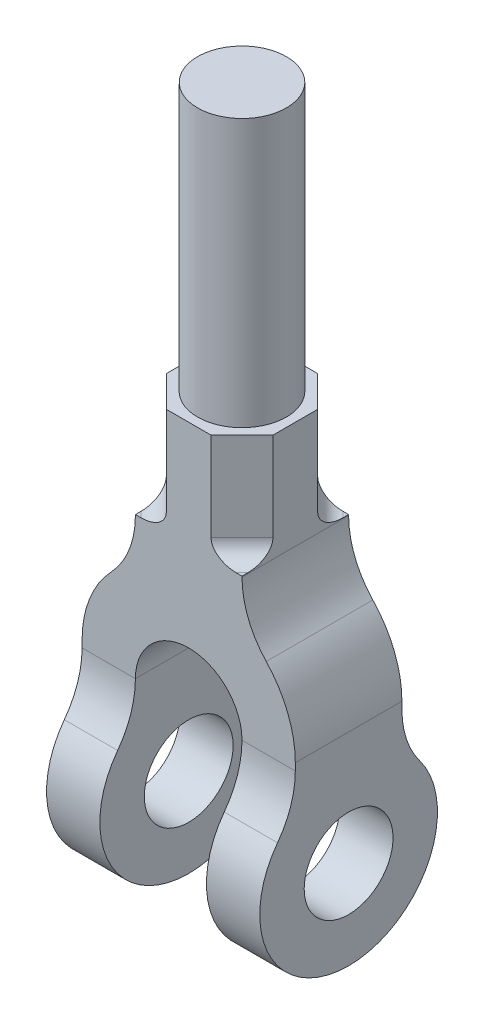
SolidWorks part; units mm, degrees
ref_plane "Front Plane" through (0, 0, 0) normal (0, 0, 1) x (1, 0, 0)
ref_plane "Top Plane" through (0, 0, 0) normal (0, 1, 0) x (1, 0, 0)
ref_plane "Right Plane" through (0, 0, 0) normal (1, 0, 0) x (0, 0, -1)
sketch "Sketch1" plane through (0, 0, 0) normal (0, 0, 1) x (1, 0, 0)
  line L1 (-60, -125) -> (60, -125)
  line L2 (-60, -125) -> (-60, 125)
  line L3 (-60, 125) -> (60, 125)
  line L4 (60, -125) -> (60, 125)
  line L5 (-60, -125) -> (60, 125) construction
  line L6 (-60, 125) -> (60, -125) construction
  point P0 (0, 0)
  dimension "D1" = 250
  dimension "D2" = 120
extrude "Boss-Extrude1" add sketch "Sketch1" along normal blind 100
sketch "Sketch2" plane through (0, 0, 100) normal (0, 0, 1) x (1, 0, 0)
  line L0 (0, 149.5031) -> (0, -100.4969) construction
  line L1 (60, 125) -> (-60, 125) construction
  line L2 (-30, 125) -> (-30, 64.4983)
  line L3 (30, 125) -> (30, 64.4983)
  line L4 (-30, -15) -> (-30, -125)
  line L7 (30, -15) -> (30, -125)
  arc A0 (-43.6364, 30.1809) -> (-30, -62.9615) centre (0, -11) ccw
  arc A1 (30, -15) -> (-30, -15) centre (0, -15) ccw
  arc A2 (-30, 64.4983) -> (-43.6364, 30.1809) centre (-80, 64.4983) cw
  arc A3 (30, 64.4983) -> (43.6364, 30.1809) centre (80, 64.4983) ccw
  arc A4 (30, -62.9615) -> (43.6364, 30.1809) centre (0, -11) ccw
  line M4 (60, -125) -> (60, 125)
  line M5 (60, 125) -> (-60, 125)
  line M6 (-60, 125) -> (-60, -125)
  line M7 (-60, -125) -> (60, -125)
  dimension "D1" = 120
  dimension "D2" = 60
  dimension "D7" = 50
  dimension "D3" = 4
  dimension "D4" = 140
  dimension "D5" = 30
  dimension "D6" = 0
  dimension "D8" = 30
extrude "Cut-Extrude1" cut sketch "Sketch2" against normal blind 100 contours A2 L2 A0 M5 M6 | A4 L3 A3 M4 M5 | A1 L0 L7 M7 | L0 A1 L4 M7 region at (20.1362, 5.1362, 100) region at (46.296, 75.3981, 100) region at (-46.296, 75.3981, 100)
sketch "Sketch3" plane through (60, 0, 0) normal (1, 0, 0) x (0, 0, -1)
  line L0 (-100, -125) -> (-100, -11) construction
  line L1 (-100, -125) -> (0, -125) construction
  line L2 (0, -125) -> (0, -11) construction
  line L4 (-80, -15) -> (-80, 125.5101)
  line L5 (-20, -15) -> (-20, 125.5101)
  line L6 (-80, 125.5101) -> (-20, 125.5101)
  arc A0 (-90, -45) -> (-10, -45) centre (-50, -75) ccw
  circle A1 centre (-50, -75) radius 25
  arc A2 (-10, -45) -> (-20, -15) centre (30, -15) cw
  arc A3 (-80, -15) -> (-90, -45) centre (-130, -15) cw
  point P12 (-20, -35)
  point P17 (-80, -35)
  dimension "D1" = 50
  dimension "D3" = 50
  dimension "D2" = 60
ref_plane "Plane1" through (70, 0, 0) normal (1, 0, 0) x (0, 0, -1)
sketch "Sketch4" plane through (70, 0, 0) normal (1, 0, 0) x (0, 0, -1)
  line L0 (-100, -125) -> (-100, 125)
  line L1 (-100, 125) -> (-80, 125)
  line L2 (0, 125) -> (-100, 125) construction
  line L3 (-20, -15) -> (-20, 125.5101)
  line L4 (-20, 125.5101) -> (-80, 125.5101)
  line L5 (-80, 125.5101) -> (-80, -15)
  line L6 (-20, -15) -> (-20, 125.5101)
  line L7 (-20, 125.5101) -> (-80, 125.5101)
  line L8 (-80, 125.5101) -> (-80, -15)
  line L9 (0, 125) -> (0, -125)
  line L10 (0, -125) -> (-100, -125)
  line L11 (-80, 125) -> (0, 125)
  circle A1 centre (-50, -75) radius 25
  circle A2 centre (-50, -75) radius 25
  arc A5 (-90, -45) -> (-10, -45) centre (-50, -75) ccw
  arc A6 (-20, -15) -> (-10, -45) centre (30, -15) ccw
  arc A7 (-90, -45) -> (-80, -15) centre (-130, -15) ccw
  arc A8 (-90, -45) -> (-10, -45) centre (-50, -75) ccw
  arc A9 (-20, -15) -> (-10, -45) centre (30, -15) ccw
  arc A10 (-90, -45) -> (-80, -15) centre (-130, -15) ccw
  dimension "D1" = 0
  dimension "D2" = 0
extrude "Cut-Extrude2" cut sketch "Sketch4" against normal blind 240 contours A8 A10 L8 L1 L0 | L6 A9 A8 L9 L11 | A8 L0 L10 | A8 L10 L9 region at (70, -113.8316, 88.8316) region at (70, 39.587, 90.3971) region at (70, -113.8316, 11.1684) region at (70, 39.587, 9.6029)
extrude "Cut-Extrude3" cut sketch "Sketch4<4>" against normal blind 240 contours A2 region at (70, -75, 50)
sketch "Sketch4<4>" plane through (70, 0, 0) normal (1, 0, 0) x (0, 0, -1) same geometry as "Sketch4"
sketch "Sketch5" plane through (0, 125, 0) normal (0, 1, 0) x (1, 0, 0)
  line L0 (0, -50) -> (0, 49950) construction
  line L1 (-30, -80) -> (30, -20)
  line L2 (12.6, -20) -> (30, -37.4)
  line L3 (-30, -20) -> (30, -20) construction
  line L4 (30, -20) -> (30, -80) construction
  line L5 (30, -62.6) -> (12.6, -80)
  line L6 (-12.6, -80) -> (-30, -62.6)
  line L7 (-30, -37.4) -> (-12.6, -20)
  circle A0 centre (0, -50) radius 25
  point P8 (0, -50)
  point P24 (0, -50)
  line M1 (30, -20) -> (-30, -20)
  line M2 (-30, -20) -> (-30, -80)
  line M3 (-30, -80) -> (30, -80)
  line M4 (30, -80) -> (30, -20)
  dimension "D2" = 50
  dimension "D1" = 0
  dimension "D3" = 17.4
  dimension "D4" = 17.4
  dimension "D5" = 4
extrude "Cut-Extrude4" cut sketch "Sketch5" against normal blind 60 contours L7 M2 M1 | L6 L1 M3 | L1 L6 M2 | L5 M4 M3 | L2 L1 M1 | L1 L2 M4 region at (-27.1, 125, 71.3) region at (-21.3, 125, 77.1) region at (-24.2, 125, 25.8) region at (24.2, 125, 74.2) region at (21.3, 125, 22.9) region at (27.1, 125, 28.7)
extrude "Boss-Extrude2" add sketch "Sketch5<3>" along normal blind 150.7 contours L1 L0 A0 | L0 A0 L1 | A0 L0 L1 | L0 L1 A0 region at (-12.0753, 125, 44.9982) region at (7.5026, 125, 57.5026) region at (6.2154, 125, 34.9947)
sketch "Sketch5<3>" plane through (0, 125, 0) normal (0, 1, 0) x (1, 0, 0) same geometry as "Sketch5"
fillet "Fillet1" radius 10 4 edges at (-21.3, 65, 71.3) (-21.3, 65, 28.7) (21.3, 65, 28.7) (21.3, 65, 71.3)
